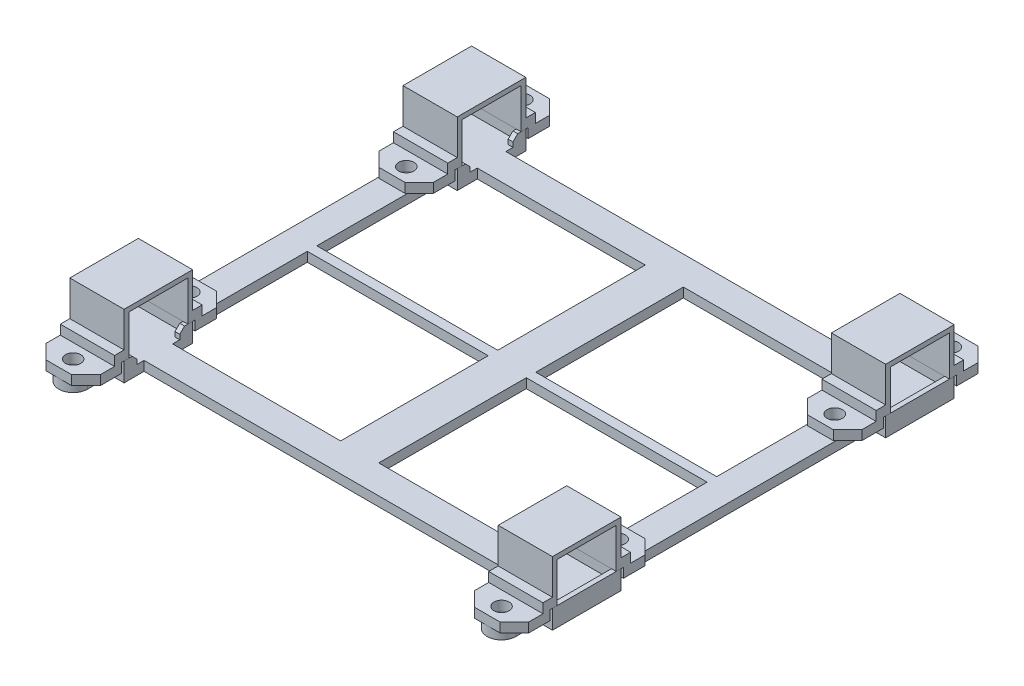
SolidWorks part; units mm, degrees
ref_plane "Front Plane" through (0, 0, 0) normal (0, 0, 1) x (1, 0, 0)
ref_plane "Top Plane" through (0, 0, 0) normal (0, 1, 0) x (1, 0, 0)
ref_plane "Right Plane" through (0, 0, 0) normal (1, 0, 0) x (0, 0, -1)
ref_axis "X" through (-88.99, 0, 0) along (1, 0, 0)
ref_axis "Y" through (0, 55, 0) along (0, -1, 0)
ref_axis "Z" through (0, 0, -88.99) along (0, 0, 1)
sketch "Sketch1" plane through (0, 0, 0) normal (0, 1, 0) x (1, 0, 0)
  line L0 (0, 0) -> (0, -32)
  line L5 (40.3, -28.8) -> (49.7, -28.8)
  line L6 (40.3, -28.8) -> (40.3, -41.2)
  line L7 (40.3, -41.2) -> (49.7, -41.2)
  line L8 (49.7, -28.8) -> (49.7, -41.2)
  line L9 (40.3, -28.8) -> (49.7, -41.2) construction
  line L10 (40.3, -41.2) -> (49.7, -28.8) construction
  line L11 (0, -35) -> (45, -35) construction
  line L15 (39.3, -27.8) -> (39.3, -42.2)
  line L16 (39.3, -42.2) -> (50.7, -42.2)
  line L17 (50.7, -27.8) -> (50.7, -42.2)
  line L18 (39.3, -27.8) -> (50.7, -27.8)
  line L19 (48, -27.8) -> (48, 0)
  line L20 (48, 0) -> (42, 0)
  line L21 (42, 0) -> (42, -27.8)
  line L22 (45, 0) -> (45, -27.8) construction
  line L23 (39.3, -32) -> (0, -32)
  line L24 (39.3, -38) -> (0, -38)
  line L25 (0, -32) -> (0, -38)
  line L26 (40.3, -30.5) -> (39.3, -30.5)
  line L27 (40.3, -39.5) -> (39.3, -39.5)
  line L28 (39.8, -30.5) -> (39.8, -39.5) construction
  line L29 (0, 0) -> (42, 0)
  line L30 (4, -32) -> (4, -1)
  line L31 (4, -1) -> (42, -1)
  line L32 (48, -47.2) -> (48, -42.2)
  line L33 (42, -47.2) -> (42, -42.2)
  circle A0 centre (45, -22.8) radius 1.6
  circle A1 centre (45, -47.2) radius 1.6
  arc A2 (42, -47.2) -> (48, -47.2) centre (45, -47.2) ccw
  point P0 (45, -35)
  point P27 (0, -35)
  point P34 (39.8, -35)
  point P41 (0, 0)
  dimension "D7" = 3.2
  dimension "D12" = 5
  dimension "D1" = 35
  dimension "D2" = 45
  dimension "D3" = 9.4
  dimension "D4" = 12.4
  dimension "D6" = 6
  dimension "D8" = 5
  dimension "D9" = 9
  dimension "D10" = 1
  dimension "D11" = 4
  dimension "D5" = 1
extrude "Boss-Extrude1" add sketch "Sketch1" against normal blind 2 contours L23 L25 L24 L15 | L20 L21 L18 L19 A0 | L30 L31 L21 L29 L0 L23 | L33 A2 L32 L16 A1 | L15 L16 L17 L18 region at (21, 0, 0.528) region at (19.65, 0, 35) region at (45, 0, 13.4491) region at (45, 0, 42.3)
extrude "Boss-Extrude2" add sketch "Sketch1<3>" along normal blind 2 contours L6 L27 L15 L16 L17 L18 L26 L5 L8 L7 region at (49.35, 0, 27.9837)
sketch "Sketch1<3>" plane through (0, 0, 0) normal (0, 1, 0) x (1, 0, 0) same geometry as "Sketch1"
sketch "Sketch2" plane through (50.7, 0, 0) normal (1, 0, 0) x (0, 0, -1)
  line L0 (-42.2, 2) -> (-42.2, 11.4)
  line L1 (-42.2, 11.4) -> (-35, 11.4)
  line L5 (-35, 10.4) -> (-41.2, 10.4)
  line L6 (-41.2, 10.4) -> (-41.2, 2)
  line L7 (-41.2, 2) -> (-42.2, 2)
  line L8 (-42.2, 2) -> (-42.7, 2)
  line L9 (-42.7, 2) -> (-42.7, 0)
  line L10 (-42.7, 0) -> (-50.2, 0)
  line L11 (-50.2, 0) -> (-50.2, 2)
  line L12 (-50.2, 2) -> (-44.2, 2)
  line L13 (-44.2, 2) -> (-44.2, 4)
  line L14 (-44.2, 4) -> (-42.2, 4)
  line L15 (-35, 11.4) -> (-35, 10.4) construction
  line L16 (-28.8, 0) -> (-41.2, 0) construction
  line L17 (-39.5, 2) -> (-41.2, 2) construction
  line L18 (-47.2, 0) -> (-42.2, 0) construction
  point P17 (-44.2013, 2)
  point P18 (-42.7, 0.0767)
  point P25 (-43.2, 3.9627)
  point P26 (-33.9917, 12.3934)
  line M16 (-27.8, 2) -> (-42.2, 2)
  dimension "D1" = 2
  dimension "D2" = 0.5
  dimension "D3" = 10.4
  dimension "D4" = 6
  dimension "D5" = 1
extrude "Boss-Extrude3" add sketch "Sketch2" against normal up to surface (11.4 mm away) separate body contours L15 L1 L0 L6 L5 M16 | L14 L13 L12 L11 L10 L9 L8 L0 region at (50.7, 1.4211, 45.7658) region at (50.7, 3, 42.0816) up to face at (39.3, 0, 39.9)
extrude "Cut-Extrude1" cut sketch "Sketch1<4>" along normal through all contours A1
sketch "Sketch1<4>" plane through (0, 0, 0) normal (0, 1, 0) x (1, 0, 0) same geometry as "Sketch1"
chamfer "Chamfer2" distance 3 angle 45 2 edges at (39.3, 1, 50.2) (50.7, 1, 50.2)
mirror "Mirror3" about plane through (20.3, 0, 35) normal (0, 0, 1) of bodies 107
chamfer "Chamfer1" distance 1 angle 45 2 edges at (39.8, 2, 39.5) (39.8, 2, 30.5)
mirror "Mirror1" about plane through (0, 0, 0) normal (1, 0, 0) of bodies 105 108 101
mirror "Mirror2" about plane through (0, 0, 0) normal (0, 0, 1) of bodies 105 109 108 110 102
combine bodies "Combine1" operation type add bodies to combine 111 112 105 109
